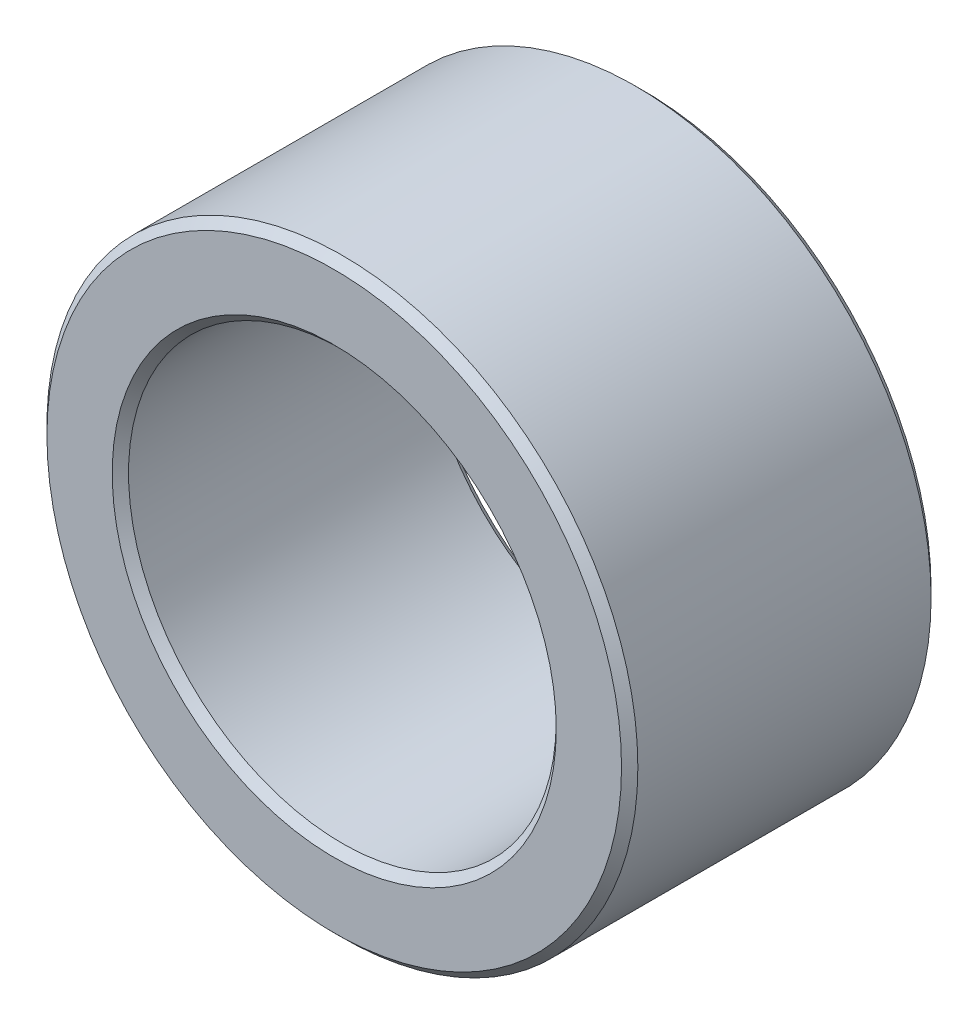
SolidWorks part; units mm, degrees
ref_plane "Front Plane" through (0, 0, 0) normal (0, 0, 1) x (1, 0, 0)
ref_plane "Top Plane" through (0, 0, 0) normal (0, 1, 0) x (1, 0, 0)
ref_plane "Right Plane" through (0, 0, 0) normal (1, 0, 0) x (0, 0, -1)
sketch "Sketch1" plane through (0, 0, 0) normal (0, 0, 1) x (1, 0, 0)
  circle A0 centre (0, 0) radius 6.6675 construction
  circle A1 centre (0, 0) radius 4.826 construction
  point P4 (0, 6.6675)
  dimension "ID" = 9.652
  dimension "OD" = 13.335
sketch "Sketch2" plane through (0, 0, 0) normal (1, 0, 0) x (0, 0, -1)
  line L0 (-3.4925, 6.6675) -> (3.4925, 6.6675) construction
  dimension "Length" = 6.985
sketch "Sketch3" plane through (0, 0, 0) normal (0, 0, 1) x (1, 0, 0)
  circle A0 centre (0, 0) radius 4.826 construction
  circle A1 centre (0, 0) radius 6.6675 construction
  circle A2 centre (0, 0) radius 4.826
  circle A3 centre (0, 0) radius 6.6675
extrude "Boss-Extrude1" add sketch "Sketch3" against normal up to vertex (3.4925 mm away) and the other way up to vertex (3.4925 mm away) up to point (0, 6.6675, -3.4925) other way up to point (0, 6.6675, 3.4925)
chamfer "Chamfer1" distance 0.1842 angle 45 4 edges at (6.6675, 0, 3.4925) (6.6675, 0, -3.4925) (4.826, 0, 3.4925) (4.826, 0, -3.4925)
equation "\"D1@Chamfer1\"=(\"OD@Sketch1\"-\"ID@Sketch1\")*0.05"
